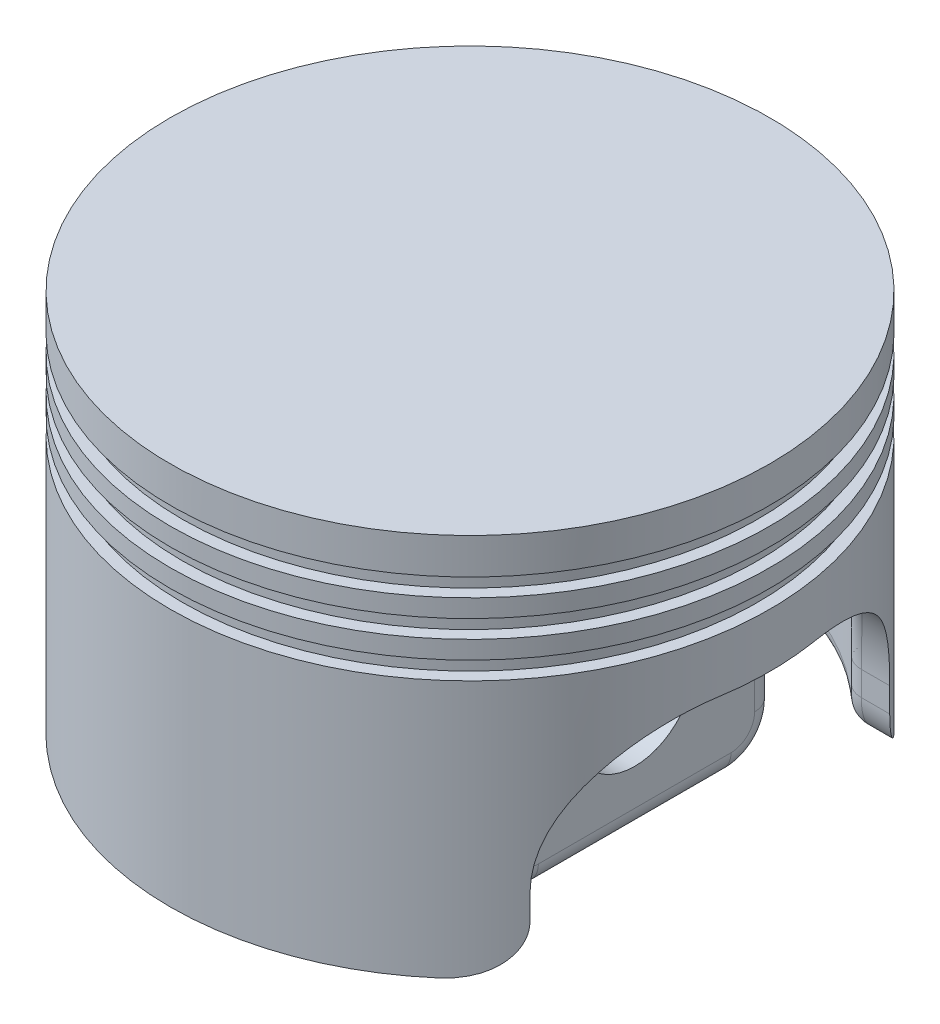
SolidWorks part; units mm, degrees
ref_plane "Front Plane" through (0, 0, 0) normal (0, 0, 1) x (1, 0, 0)
ref_plane "Top Plane" through (0, 0, 0) normal (0, 1, 0) x (1, 0, 0)
ref_plane "Right Plane" through (0, 0, 0) normal (1, 0, 0) x (0, 0, -1)
sketch "Sketch1" plane through (0, 0, 0) normal (0, 0, 1) x (1, 0, 0)
  line L0 (0, 0) -> (0, -19)
  line L1 (0, -19) -> (57.15, -19)
  line L2 (57.15, -19) -> (57.15, -81.28)
  line L3 (57.15, -81.28) -> (63.5, -81.28)
  line L4 (63.5, -81.28) -> (63.5, 0)
  line L5 (63.5, 0) -> (0, 0)
  dimension "D1" = 63.5
  dimension "D2" = 81.28
  dimension "D3" = 57.15
  dimension "D4" = 19
revolve "Revolve1" add sketch "Sketch1" angle 360 about L0
sketch "Sketch2" plane through (0, 0, 0) normal (1, 0, 0) x (0, 0, -1)
  line L0 (-63.5, -81.28) -> (63.5, -81.28) construction
  line L1 (38.1, -81.28) -> (-38.1, -81.28)
  line L2 (38.1, -81.28) -> (38.1, -38.1)
  line L3 (38.1, -38.1) -> (-38.1, -38.1)
  line L4 (-38.1, -81.28) -> (-38.1, -38.1)
  line L5 (38.1, -81.28) -> (-38.1, -38.1) construction
  line L6 (38.1, -38.1) -> (-38.1, -81.28) construction
  point P0 (0, -59.69)
  dimension "D1" = 76.2
  dimension "D2" = 43.18
extrude "Cut-Extrude1" cut sketch "Sketch2" against normal through all both and the other way through all
sketch "Sketch3" plane through (0, 0, 0) normal (1, 0, 0) x (0, 0, -1)
  line L0 (0, 0) -> (0, -29.8967) construction
  line L1 (63.5, -81.28) -> (63.5, 0) construction
  line L2 (60.96, -7.62) -> (66.04, -7.62)
  line L3 (60.96, -7.62) -> (60.96, -11.43)
  line L4 (60.96, -11.43) -> (66.04, -11.43)
  line L5 (66.04, -7.62) -> (66.04, -11.43)
  line L6 (60.96, -7.62) -> (66.04, -11.43) construction
  line L7 (60.96, -11.43) -> (66.04, -7.62) construction
  line L8 (63.5, 0) -> (-63.5, 0) construction
  point P3 (63.5, -9.525)
  dimension "D1" = 3.81
  dimension "D2" = 2.54
  dimension "D3" = 7.62
revolve "Cut-Revolve1" cut sketch "Sketch3" angle 360 about L0
pattern_linear "LPattern1" count 3 spacing 7.62 along (0, -1, 0) of "Cut-Revolve1"
sketch "Sketch4" plane through (0, -19, 0) normal (0, -1, 0) x (1, 0, 0)
  line L0 (0, 0) -> (0, 28.9575) construction
  line L1 (34.88, 30.4) -> (15.88, 30.4)
  line L2 (-34.88, -30.4) -> (-15.88, -30.4)
  line L3 (-34.88, -30.4) -> (-34.88, 30.4)
  line L4 (-34.88, 30.4) -> (-15.88, 30.4)
  line L5 (-15.88, -30.4) -> (-15.88, 30.4)
  line L6 (-34.88, -30.4) -> (-15.88, 30.4) construction
  line L7 (-34.88, 30.4) -> (-15.88, -30.4) construction
  line L8 (15.88, -30.4) -> (15.88, 30.4)
  line L9 (34.88, -30.4) -> (15.88, -30.4)
  line L10 (34.88, -30.4) -> (34.88, 30.4)
  point P3 (-25.38, 0)
  dimension "D1" = 60.8
  dimension "D2" = 19
  dimension "D3" = 31.76
extrude "Boss-Extrude1" add sketch "Sketch4" along normal blind 63.5
sketch "Sketch5" plane through (-34.88, 0, 0) normal (-1, 0, 0) x (0, 0, 1)
  line L0 (30.4, -82.5) -> (-30.4, -82.5) construction
  circle A0 centre (0, -57.1) radius 12.7
  dimension "D1" = 25.4
  dimension "D2" = 25.4
extrude "Cut-Extrude2" cut sketch "Sketch5" against normal through all both and the other way through all
fillet "Fillet1" radius 28 4 edges at (46.6985, -38.1, -38.1) (46.6985, -38.1, 38.1) (-46.6985, -38.1, 38.1) (-46.6985, -38.1, -38.1)
fillet "Fillet2" radius 10 8 edges at (-46.6985, -81.28, -38.1) (46.6985, -81.28, -38.1) (46.6985, -81.28, 38.1) (-46.6985, -81.28, 38.1) (-25.38, -82.5, -30.4) (-25.38, -82.5, 30.4) (25.38, -82.5, -30.4) (25.38, -82.5, 30.4)
fillet "Fillet3" radius 5 36 edges at (34.88, -45.75, -30.4) (34.88, -79.5711, -27.4711) (34.88, -45.75, 30.4) (34.88, -79.5711, 27.4711) (15.88, -45.75, 30.4) (15.88, -79.5711, 27.4711) (15.88, -45.75, -30.4) (15.88, -79.5711, -27.4711) (-15.88, -45.75, -30.4) (-15.88, -79.5711, -27.4711) (-15.88, -45.75, 30.4) (-15.88, -79.5711, 27.4711) (-34.88, -45.75, 30.4) (-34.88, -79.5711, 27.4711) (-34.88, -45.75, -30.4) (-34.88, -79.5711, -27.4711) (-40.0022, -78.1316, 40.816) (-42.5971, -68.69, 38.1) (-46.055, -51.2516, 33.8387) (-57.15, -38.1, 0) (-50.4318, -43.6881, -26.8841) (-42.5971, -68.69, -38.1) (-41.3657, -76.2692, -39.4335) (0, -81.28, -57.15) (40.0022, -78.1316, -40.816) (42.5971, -68.69, -38.1) (46.055, -51.2516, -33.8387) (57.15, -38.1, 0) (50.4318, -43.6881, 26.8841) (42.5971, -68.69, 38.1) (41.3657, -76.2692, 39.4335) (34.88, -82.5, 0) (15.88, -82.5, 0) (-15.88, -82.5, 0) (-34.88, -82.5, 0) (0, -81.28, 57.15)
fillet "Fillet4" radius 5 17 edges at (33.4155, -19, 28.9355) (25.38, -19, 30.4) (17.3445, -19, 28.9355) (15.88, -19, 0) (17.3445, -19, -28.9355) (25.38, -19, -30.4) (33.4155, -19, -28.9355) (34.88, -19, 0) (-57.15, -19, 0) (-17.3445, -19, 28.9355) (-25.38, -19, 30.4) (-33.4155, -19, 28.9355) (-34.88, -19, 0) (-33.4155, -19, -28.9355) (-25.38, -19, -30.4) (-17.3445, -19, -28.9355) (-15.88, -19, 0)
